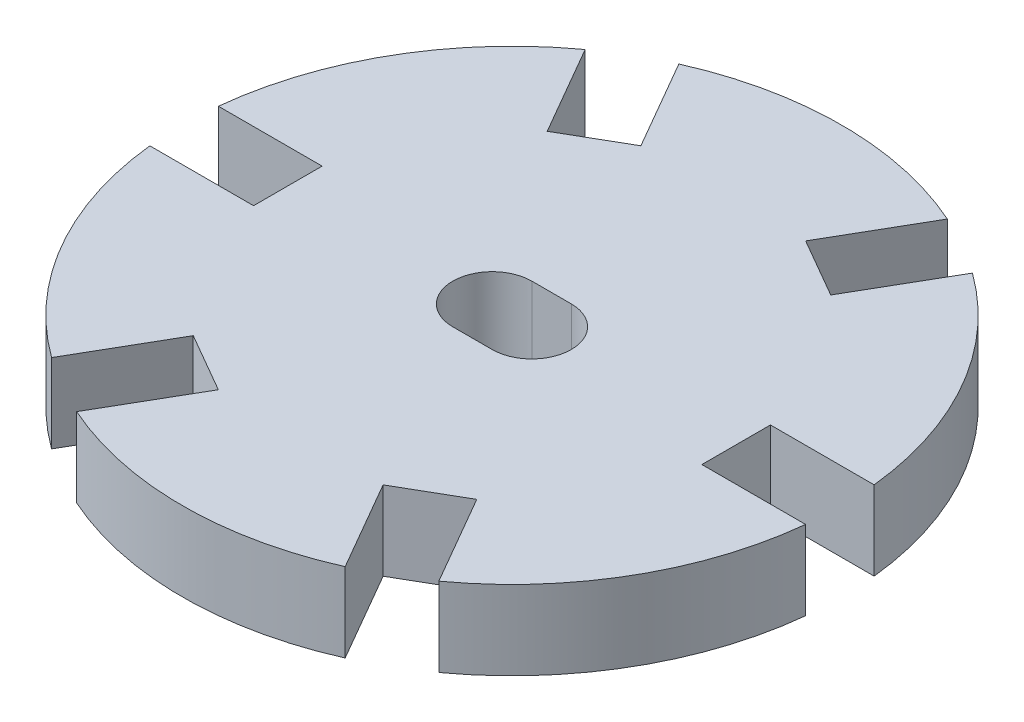
SolidWorks part; units mm, degrees
ref_plane "Front Plane" through (0, 0, 0) normal (0, 0, 1) x (1, 0, 0)
ref_plane "Top Plane" through (0, 0, 0) normal (0, 1, 0) x (1, 0, 0)
ref_plane "Right Plane" through (0, 0, 0) normal (1, 0, 0) x (0, 0, -1)
sketch "Sketch1" plane through (0, 0, 0) normal (0, 1, 0) x (1, 0, 0)
  circle A0 centre (0, 0) radius 12.5
  dimension "D1" = 25
extrude "Boss-Extrude1" add sketch "Sketch1" along normal blind 1.5 and the other way blind 1.5
sketch "Sketch2" plane through (0, 1.5, 0) normal (0, 1, 0) x (1, 0, 0)
  line L0 (9.3758, 13.6394) -> (5.3758, 6.7112)
  line L1 (16.5, -1.3) -> (8.5, -1.3)
  line L2 (16.5, -1.3) -> (16.5, 1.3)
  line L3 (16.5, 1.3) -> (8.5, 1.3)
  line L4 (8.5, -1.3) -> (8.5, 1.3)
  line L5 (12.5, 1.3) -> (12.5, -1.3) construction
  line L6 (16.5, 0) -> (8.5, 0) construction
  line L7 (9.3758, 13.6394) -> (7.1242, 14.9394)
  line L8 (7.1242, 14.9394) -> (3.1242, 8.0112)
  line L9 (5.3758, 6.7112) -> (3.1242, 8.0112)
  line L10 (5.1242, 11.4753) -> (7.3758, 10.1753) construction
  line L11 (8.25, 14.2894) -> (4.25, 7.3612) construction
  line L12 (-7.1242, 14.9394) -> (-3.1242, 8.0112)
  line L13 (-7.1242, 14.9394) -> (-9.3758, 13.6394)
  line L14 (-9.3758, 13.6394) -> (-5.3758, 6.7112)
  line L15 (-3.1242, 8.0112) -> (-5.3758, 6.7112)
  line L16 (-7.3758, 10.1753) -> (-5.1242, 11.4753) construction
  line L17 (-8.25, 14.2894) -> (-4.25, 7.3612) construction
  line L18 (-16.5, 1.3) -> (-8.5, 1.3)
  line L19 (-16.5, 1.3) -> (-16.5, -1.3)
  line L20 (-16.5, -1.3) -> (-8.5, -1.3)
  line L21 (-8.5, 1.3) -> (-8.5, -1.3)
  line L22 (-12.5, -1.3) -> (-12.5, 1.3) construction
  line L23 (-16.5, 0) -> (-8.5, 0) construction
  line L24 (-9.3758, -13.6394) -> (-5.3758, -6.7112)
  line L25 (-9.3758, -13.6394) -> (-7.1242, -14.9394)
  line L26 (-7.1242, -14.9394) -> (-3.1242, -8.0112)
  line L27 (-5.3758, -6.7112) -> (-3.1242, -8.0112)
  line L28 (-5.1242, -11.4753) -> (-7.3758, -10.1753) construction
  line L29 (-8.25, -14.2894) -> (-4.25, -7.3612) construction
  line L30 (7.1242, -14.9394) -> (3.1242, -8.0112)
  line L31 (7.1242, -14.9394) -> (9.3758, -13.6394)
  line L32 (9.3758, -13.6394) -> (5.3758, -6.7112)
  line L33 (3.1242, -8.0112) -> (5.3758, -6.7112)
  line L34 (7.3758, -10.1753) -> (5.1242, -11.4753) construction
  line L35 (8.25, -14.2894) -> (4.25, -7.3612) construction
  circle A0 centre (0, 0) radius 12.5 construction
  point P0 (12.5, 0)
  point P9 (6.25, 10.8253)
  point P18 (-6.25, 10.8253)
  point P27 (-12.5, 0)
  point P36 (-6.25, -10.8253)
  point P45 (6.25, -10.8253)
  point P54 (0, 0)
  dimension "D1" = 2.6
  dimension "D2" = 4
  dimension "D3" = 6
extrude "Cut-Extrude1" cut sketch "Sketch2" against normal through all
sketch "Sketch3" plane through (0, 0, 0) normal (0, 1, 0) x (1, 0, 0)
  line L2 (0.6468, 0) -> (-0.6468, 0) construction
  line L3 (0.6468, -1.5) -> (-0.6468, -1.5) construction
  line L4 (0.6468, 1.5) -> (-0.6468, 1.5) construction
  line L5 (-2.1468, 1.5) -> (-2.1468, -1.5) construction
  line L6 (-0.7468, 0) -> (0.7468, 0) construction
  line L7 (-0.7468, 1.5) -> (0.7468, 1.5)
  line L8 (-0.7468, -1.5) -> (0.7468, -1.5)
  arc A2 (0.6468, -1.5) -> (0.6468, 1.5) centre (0.6468, 0) ccw construction
  arc A3 (-0.6468, 1.5) -> (-0.6468, -1.5) centre (-0.6468, 0) ccw construction
  arc A4 (-0.7468, 1.5) -> (-0.7468, -1.5) centre (-0.7468, 0) ccw
  arc A5 (0.7468, -1.5) -> (0.7468, 1.5) centre (0.7468, 0) ccw
  point P2 (0, 0)
  point P11 (0, 0)
  dimension "D1" = 3
  dimension "D2" = 0.1
extrude "Cut-Extrude2" cut sketch "Sketch3" against normal through all both and the other way through all
